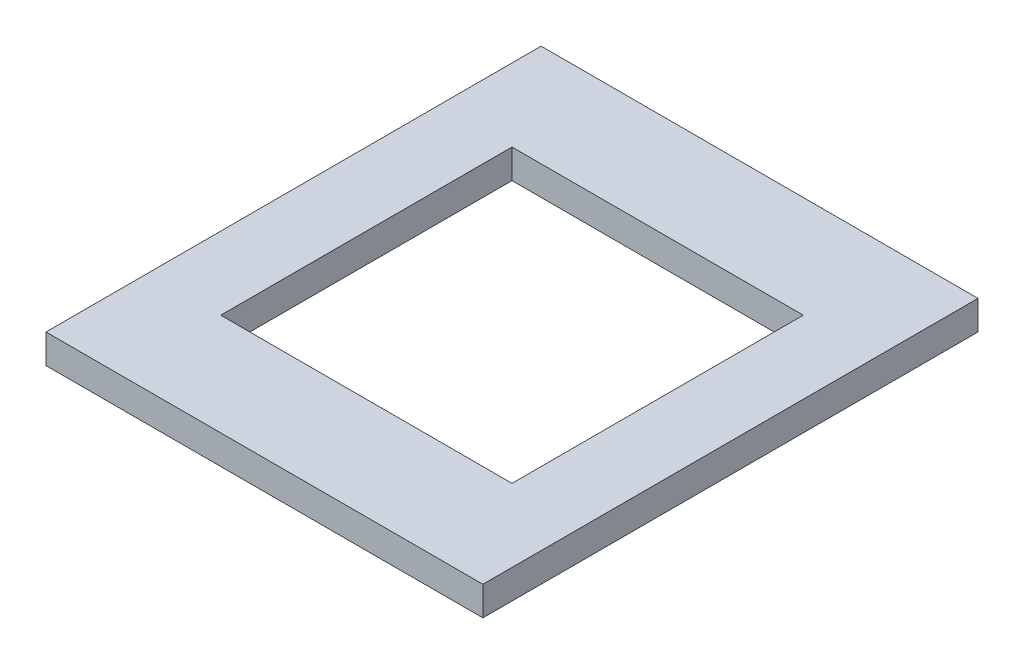
SolidWorks part; units mm, degrees
ref_plane "Front Plane" through (0, 0, 0) normal (0, 0, 1) x (1, 0, 0)
ref_plane "Top Plane" through (0, 0, 0) normal (0, 1, 0) x (1, 0, 0)
ref_plane "Right Plane" through (0, 0, 0) normal (1, 0, 0) x (0, 0, -1)
sketch "Sketch1" plane through (0, 0, 0) normal (0, 1, 0) x (1, 0, 0)
  line L1 (0, 0) -> (-150, 0)
  line L2 (0, 0) -> (0, 30)
  line L3 (0, 30) -> (-150, 30)
  line L4 (-150, 0) -> (-150, 30)
  dimension "D1" = 30
  dimension "D2" = 150
extrude "Boss-Extrude1" add sketch "Sketch1" along normal blind 10
sketch "Sketch8" plane through (0, 0, 0) normal (0, -1, 0) x (-1, 0, 0)
  line L0 (150, 0) -> (0, 30)
  line L1 (150, 30) -> (0, 0)
  line L2 (150, 0) -> (0, 0) construction
sketch "Sketch9" plane through (0, 0, 0) normal (0, -1, 0) x (1, 0, 0)
  line L0 (-150, -30) -> (0, 0) construction
  line L1 (0, -100) -> (-150, -100)
  line L2 (0, -100) -> (0, 70)
  line L3 (0, 70) -> (-150, 70)
  line L4 (-150, -100) -> (-150, 70)
  line L5 (0, -100) -> (-150, 70) construction
  line L6 (0, 70) -> (-150, -100) construction
  line L8 (-125, -65) -> (-25, -65)
  line L9 (-125, -65) -> (-125, 35)
  line L10 (-125, 35) -> (-25, 35)
  line L11 (-25, -65) -> (-25, 35)
  line L12 (-125, -65) -> (-25, 35) construction
  line L13 (-125, 35) -> (-25, -65) construction
  point P0 (-75, -15)
  point P7 (-75, -15)
  point P12 (-75, 70)
  point P13 (-75, -100)
  dimension "D1" = 170
  dimension "D2" = 150
  dimension "D3" = 100
  dimension "D4" = 100
extrude "Boss-Extrude3" add sketch "Sketch9" along normal blind 10
sketch "Sketch19" plane through (0, -10, 0) normal (0, -1, 0) x (1, 0, 0)
  line L0 (-125, 35) -> (-125, 70)
  line L1 (0, 70) -> (-150, 70) construction
  line L2 (-25, 35) -> (-25, 70)
  line L3 (-125, 52.5) -> (-25, 52.5)
  line L4 (-125, -15) -> (-25, -15)
  line L5 (-125, 35) -> (-125, -65) construction
  line L6 (-25, -65) -> (-25, 35) construction
ref_point "Point1"
sketch "Sketch25" plane through (0, 0, 0) normal (0, 1, 0) x (1, 0, 0)
  line L1 (0, 30) -> (-150, 30)
  line L2 (0, 30) -> (0, 0)
  line L3 (0, 0) -> (-150, 0)
  line L4 (-150, 30) -> (-150, 0)
extrude "Cut-Extrude2" cut sketch "Sketch25" along normal blind 10
ref_point "Point2"
ref_point "Point3"
